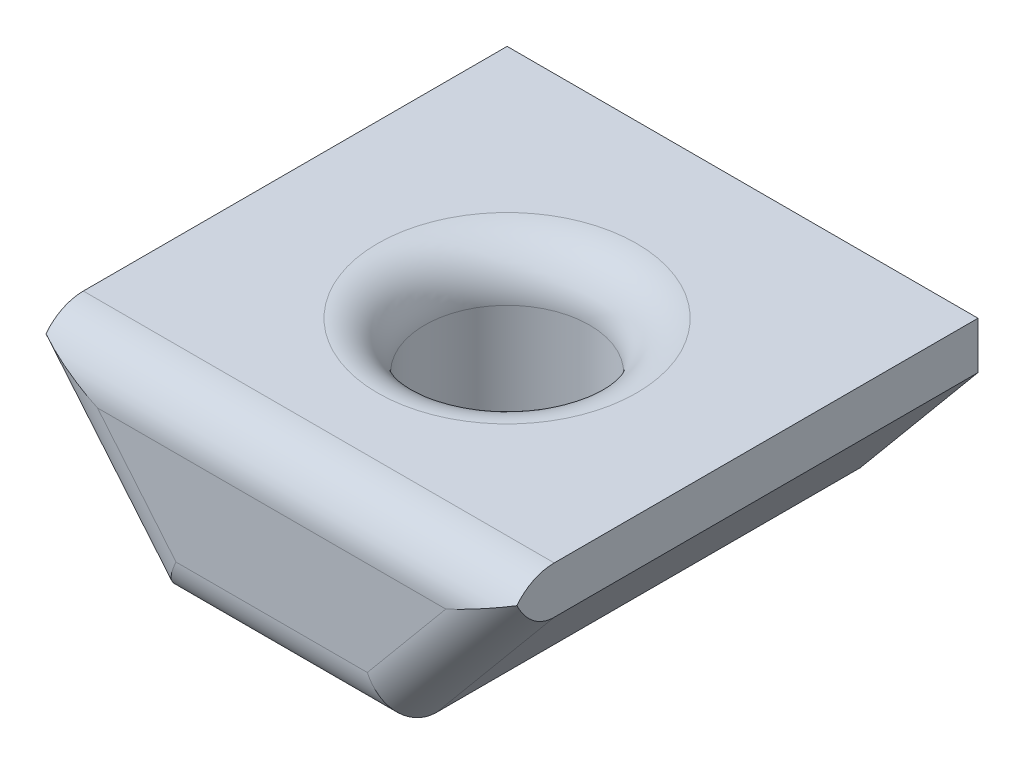
SolidWorks part; units mm, degrees
ref_plane "Front Plane" through (0, 0, 0) normal (0, 0, 1) x (1, 0, 0)
ref_plane "Top Plane" through (0, 0, 0) normal (0, 1, 0) x (1, 0, 0)
ref_plane "Right Plane" through (0, 0, 0) normal (1, 0, 0) x (0, 0, -1)
sketch "Sketch1" plane through (0, 0, 0) normal (0, 0, 1) x (1, 0, 0)
  line L0 (0, 0) -> (0, -18145.3617) construction
  line L1 (-2.5, 0) -> (2.5, 0)
  line L2 (2.5, 0) -> (5, 3)
  line L3 (5, 3) -> (5, 4)
  line L4 (5, 4) -> (-5, 4)
  line L5 (-5, 3) -> (-5, 4)
  line L6 (-2.5, 0) -> (-5, 3)
  point P9 (0, 4)
  point P11 (0, 0)
  dimension "D1" = 2.5
  dimension "D2" = 5
  dimension "D3" = 3
  dimension "D4" = 1
extrude "Boss-Extrude1" add sketch "Sketch1" along normal blind 10
sketch "Sketch3" plane through (0, 4, 0) normal (0, 1, 0) x (1, 0, 0)
  line L1 (5, -10) -> (5, 0) construction
  circle A0 centre (0, -5) radius 1.75
  point P5 (5, -5)
  dimension "D1" = 3.5
extrude "Cut-Extrude1" cut sketch "Sketch3" against normal through all
fillet "Fillet2" radius 1 5 edges at (0, 0, 10) (3.75, 1.5, 10) (-3.75, 1.5, 10) (0, 4, 10) (0, 4, 6.75)
